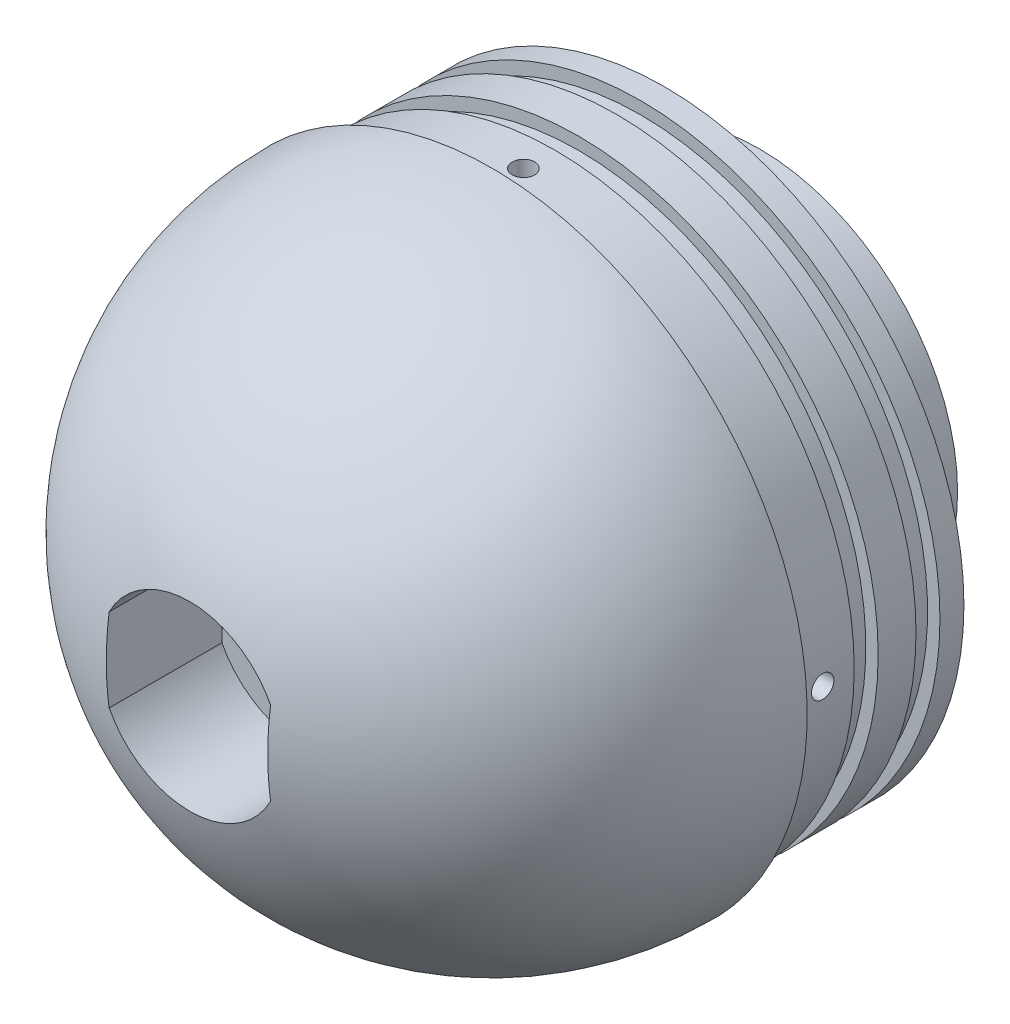
SolidWorks part; units mm, degrees
material "6061-T6 (SS)"
ref_plane "XY" through (0, 0, 0) normal (0, 0, 1) x (1, 0, 0)
ref_plane "XZ" through (0, 0, 0) normal (0, 1, 0) x (1, 0, 0)
ref_plane "YZ" through (0, 0, 0) normal (1, 0, 0) x (0, 0, -1)
ref_axis "X" through (-34.925, 0, 0) along (1, 0, 0)
ref_axis "Y" through (0, -34.925, 0) along (0, 1, 0)
ref_axis "Z" through (0, 0, 50.4955) along (0, 0, -1)
sketch "Sketch2" plane through (0, 0, 0) normal (1, 0, 0) x (0, 0, -1)
  line L2 (-17.399, 30.1371) -> (-11.049, 30.1371)
  line L3 (-11.049, 30.1371) -> (-11.049, 28.8925)
  line L4 (-11.049, 28.8925) -> (-8.636, 28.8925)
  line L5 (-8.636, 28.8925) -> (-8.636, 30.1371)
  line L6 (-8.636, 30.1371) -> (-4.826, 30.1371)
  line L7 (-4.826, 30.1371) -> (-4.826, 28.8925)
  line L8 (-4.826, 28.8925) -> (-2.413, 28.8925)
  line L9 (-2.413, 28.8925) -> (-2.413, 30.1371)
  line L10 (-2.413, 30.1371) -> (0, 30.1371)
  line L11 (0, 30.1371) -> (0, 0)
  line L12 (0, 0) -> (-17.399, 0)
  line L13 (-17.399, 30.1371) -> (-17.399, 0)
  dimension "D1" = 30.1371
  dimension "D2" = 28.8925
  dimension "D3" = 2.413
  dimension "D4" = 3.81
  dimension "D5" = 2.413
  dimension "D7" = 6.35
revolve "Revolve1" add sketch "Sketch2" angle 360 about L12
hole_wizard "#4-40 Tapped Hole1" positions "3DSketch1" profile "Sketch3" tap size "#4-40" standard "ANSI Inch"
sketch3d "3DSketch1"
  line L0 (0, 0, 0) -> (0, 0, 14.224)
  line L1 (0, 0, 14.224) -> (-30.1371, 0, 14.224)
  line L3 (30.1371, 0, 14.224) -> (0, -30.1371, 14.224)
  line L5 (0, -30.1371, 14.224) -> (-30.1371, 0, 14.224)
  line L9 (0, 0, 14.224) -> (0, -30.1371, 14.224)
  line L11 (0, 0, 14.224) -> (30.1371, 0, 14.224)
  line L13 (0, 0, 14.224) -> (0, 30.1371, 14.224)
  line L15 (0, -30.1371, 11.049) -> (0, -30.1371, 17.399)
  line L16 (0, 30.1371, 14.224) -> (-30.1371, 0, 14.224)
  line L18 (30.1371, 0, 14.224) -> (0, 30.1371, 14.224)
  circle A1 centre (0, 0, 11.049) radius 30.1371 construction
  circle A2 centre (0, 0, 17.399) radius 30.1371 construction
  point P5 (0, -30.1371, 14.224)
  point P7 (30.1371, 0, 14.224)
  point P20 (-30.1371, 0, 14.224)
  point P1370 (0, 0, -19.0881)
  point P1373 (0, 0, -12.7381)
  point P1390 (0, 30.1371, 14.224)
cosmetic thread "Hole Thread2" parameters "D1"=5.588, "D2"=2.8448
cosmetic thread "Hole Thread3" parameters "D1"=5.588, "D2"=2.8448
cosmetic thread "Hole Thread5" parameters "D1"=5.588, "D2"=2.8448
cosmetic thread "Hole Thread6" parameters "D1"=5.588, "D2"=2.8448
sketch "Sketch3" plane through (0, -30.1371, 14.224) normal (1, 0, 0) x (0, 0, -1)
  line L0 (0, 0) -> (0, 8.2992)
  line L1 (0, 8.2992) -> (1.1303, 7.62)
  line L2 (1.1303, 7.62) -> (1.1303, 0)
  line L5 (1.1303, 0) -> (0, 0)
  line L10 (0, 8.2992) -> (-1.1303, 7.62) construction
  line L11 (0, -6.35) -> (0, 107.95) construction
  dimension "Tap Drill Dia." = 2.2606
  dimension "Tap Drill Depth" = 7.62
  dimension "Drill Angle" = 118
sketch "Sketch6" plane through (0, 0, 0) normal (0, 1, 0) x (1, 0, 0)
  line L0 (0, -17.399) -> (31.75, -17.399)
  line L1 (-30.1371, -17.399) -> (30.1371, -17.399) construction
  line L2 (0, -17.399) -> (0, -49.149)
  arc A0 (0, -49.149) -> (31.75, -17.399) centre (0, -17.399) ccw
  dimension "D1" = 31.75
revolve "Revolve2" add sketch "Sketch6" angle 360 about L2
ref_plane "Plane1" through (0, 0, 49.149) normal (0, 0, 1) x (1, 0, 0)
sketch "Sketch8" plane through (0, 0, 49.149) normal (0, 0, 1) x (1, 0, 0)
  line L1 (-8.128, 4.1891) -> (8.128, 4.1891) construction
  line L2 (-8.128, 4.1891) -> (-8.128, -4.1891)
  line L3 (-8.128, -4.1891) -> (8.128, -4.1891) construction
  line L4 (8.128, 4.1891) -> (8.128, -4.1891)
  line L5 (-8.128, 4.1891) -> (8.128, -4.1891) construction
  line L6 (-8.128, -4.1891) -> (8.128, 4.1891) construction
  arc A0 (8.128, 4.1891) -> (-8.128, 4.1891) centre (0, 0) ccw
  arc A1 (-8.128, -4.1891) -> (8.128, -4.1891) centre (0, 0) ccw
  dimension "D1" = 18.288
  dimension "D2" = 16.256
extrude "Cut-Extrude1" cut sketch "Sketch8" against normal blind 12.7
sketch "Sketch9" plane through (0, 0, 36.449) normal (0, 0, 1) x (1, 0, 0)
  circle A0 centre (0, 0) radius 5.1
  dimension "D1" = 10.2
extrude "Cut-Extrude2" cut sketch "Sketch9" against normal through all
sketch "Sketch10" plane through (0, 0, 0) normal (0, 0, -1) x (-1, 0, 0)
  circle A0 centre (0, 0) radius 19.9478
extrude "Cut-Extrude3" cut sketch "Sketch10" against normal offset from surface (28.449 mm away) 8 up to face at (5.1, 0, 36.449)
hole_wizard "#8-32 Tapped Hole1" positions "Sketch11" profile "Sketch12" tap size "#8-32" standard "ANSI Inch"
sketch "Sketch11" plane through (0, 0, 28.449) normal (0, 0, -1) x (-1, 0, 0)
  line L1 (0, 0) -> (-5.1, 0) construction
  line L2 (-5.1, 0) -> (-19.9478, 0) construction
  line L5 (5.1, 0) -> (19.9478, 0) construction
  circle A0 centre (0, 0) radius 5.1 construction
  circle A1 centre (0, 0) radius 19.9478 construction
  point P25 (-12.5239, 0)
  point P27 (12.5239, 0)
cosmetic thread "Hole Thread7" parameters "D1"=8.382, "D2"=4.1656
cosmetic thread "Hole Thread8" parameters "D1"=8.382, "D2"=4.1656
sketch "Sketch12" plane through (-12.5239, 0, 28.449) normal (1, 0, 0) x (0, 1, 0)
  line L0 (0, 0) -> (0, 11.7058)
  line L1 (0, 11.7058) -> (1.7272, 10.668)
  line L2 (1.7272, 10.668) -> (1.7272, 0)
  line L5 (1.7272, 0) -> (0, 0)
  line L10 (0, 11.7058) -> (-1.7272, 10.668) construction
  line L11 (0, -6.35) -> (0, 107.95) construction
  dimension "Tap Drill Dia." = 3.4544
  dimension "Tap Drill Depth" = 10.668
  dimension "Drill Angle" = 118
sketch "Sketch13" plane through (0, 0, 28.449) normal (0, 0, -1) x (-1, 0, 0)
  circle A0 centre (0, 0) radius 19.9478
  circle A1 centre (0, 0) radius 19.9478 construction
extrude "Boss-Extrude1" add sketch "Sketch13" along normal blind 38 separate body
sketch "Sketch14" plane through (0, 0, 0) normal (0, 0, -1) x (-1, 0, 0)
  line L0 (-26.7745, -3.175) -> (-20.4245, -3.175)
  line L1 (-20.4245, -3.175) -> (-20.4245, 3.175)
  line L2 (-20.4245, 3.175) -> (-26.7745, 3.175)
  line L3 (0, 0) -> (-20.4245, 0) construction
  line L4 (-3.175, 26.7745) -> (-3.175, 20.4245)
  line L5 (-3.175, 20.4245) -> (3.175, 20.4245)
  line L6 (3.175, 20.4245) -> (3.175, 26.7745)
  line L7 (26.7745, 3.175) -> (20.4245, 3.175)
  line L8 (20.4245, 3.175) -> (20.4245, -3.175)
  line L9 (20.4245, -3.175) -> (26.7745, -3.175)
  line L10 (3.175, -26.7745) -> (3.175, -20.4245)
  line L11 (3.175, -20.4245) -> (-3.175, -20.4245)
  line L12 (-3.175, -20.4245) -> (-3.175, -26.7745)
  line L13 (0, 0) -> (0, 20.4245) construction
  arc A0 (-26.7745, -3.175) -> (-3.175, -26.7745) centre (0, 0) ccw
  circle A1 centre (0, 0) radius 30.1371 construction
  arc A2 (3.175, -26.7745) -> (26.7745, -3.175) centre (0, 0) ccw
  arc A3 (-3.175, 26.7745) -> (-26.7745, 3.175) centre (0, 0) ccw
  arc A4 (26.7745, 3.175) -> (3.175, 26.7745) centre (0, 0) ccw
  dimension "D1" = 3.175
  dimension "D2" = 6.35
  dimension "D3" = 6.35
  dimension "D4" = 4
extrude "Cut-Extrude4" cut sketch "Sketch14" against normal up to surface (28.449 mm away) up to face at (10.7967, 0, 28.449)
fillet "Fillet1" radius 6.858 8 edges at (26.7745, -3.175, 14.2245) (26.7745, 3.175, 14.2245) (3.175, 26.7745, 14.2245) (-3.175, 26.7745, 14.2245) (-26.7745, 3.175, 14.2245) (-26.7745, -3.175, 14.2245) (-3.175, -26.7745, 14.2245) (3.175, -26.7745, 14.2245)
